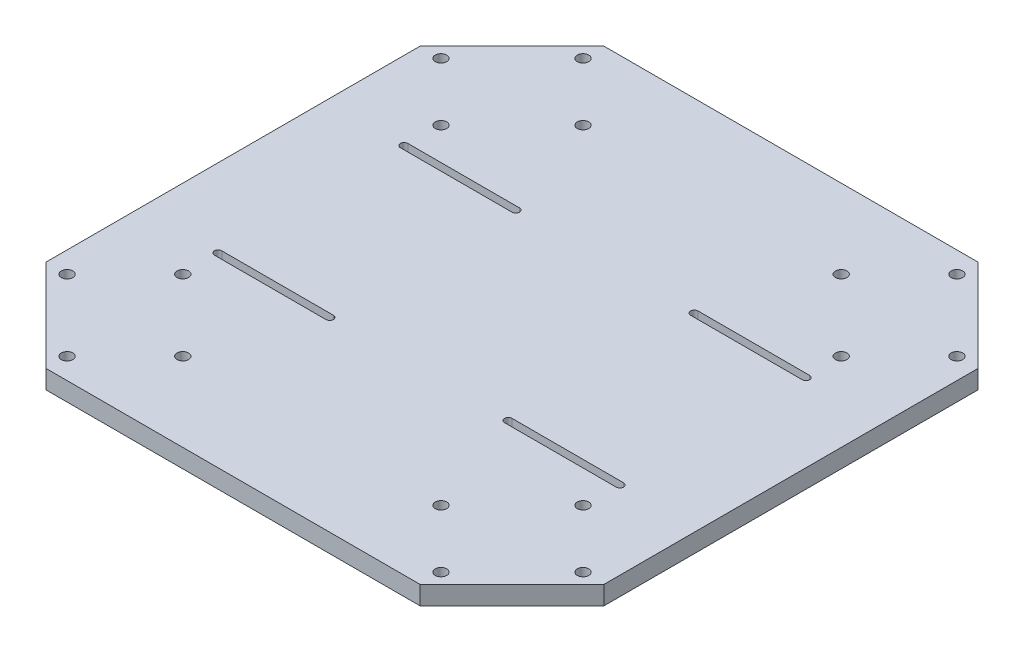
SolidWorks part; units mm, degrees
ref_plane "Front Plane" through (0, 0, 0) normal (0, 0, 1) x (1, 0, 0)
ref_plane "Top Plane" through (0, 0, 0) normal (0, 1, 0) x (1, 0, 0)
ref_plane "Right Plane" through (0, 0, 0) normal (1, 0, 0) x (0, 0, -1)
sketch "Sketch1" plane through (0, 0, 0) normal (0, 1, 0) x (1, 0, 0)
  line L1 (-75, 75) -> (75, 75)
  line L2 (-75, 75) -> (-75, -75)
  line L3 (-75, -75) -> (75, -75)
  line L4 (75, 75) -> (75, -75)
  line L5 (-75, 75) -> (75, -75) construction
  line L6 (-75, -75) -> (75, 75) construction
  point P0 (0, 0)
  dimension "D1" = 150
extrude "Boss-Extrude1" add sketch "Sketch1" along normal mid plane 5
sketch "Sketch2" plane through (0, 2.5, 0) normal (0, 1, 0) x (1, 0, 0)
  line L0 (50.2513, 75) -> (75, 75)
  line L1 (-15, 15) -> (15, 15)
  line L2 (-15, 15) -> (-15, -15)
  line L3 (-15, -15) -> (15, -15)
  line L4 (15, 15) -> (15, -15)
  line L5 (-15, 15) -> (15, -15) construction
  line L6 (-15, -15) -> (15, 15) construction
  line L7 (75, 75) -> (-75, 75) construction
  line L8 (75, -75) -> (75, 75) construction
  line L9 (75, 75) -> (75, 50.2513)
  line L10 (75, 50.2513) -> (50.2513, 75)
  line L11 (0, 0) -> (-24.6603, 0) construction
  line L12 (0, 0) -> (0, -37.7235) construction
  line L13 (-75, 75) -> (-75, 50.2513)
  line L14 (-50.2513, 75) -> (-75, 75)
  line L15 (-75, 50.2513) -> (-50.2513, 75)
  line L16 (-50.2513, -75) -> (-75, -75)
  line L17 (-75, -50.2513) -> (-50.2513, -75)
  line L18 (-75, -75) -> (-75, -50.2513)
  line L19 (75, -75) -> (75, -50.2513)
  line L20 (50.2513, -75) -> (75, -75)
  line L21 (75, -50.2513) -> (50.2513, -75)
  point P0 (0, 0)
  dimension "D1" = 30
  dimension "D2" = 35
extrude "Cut-Extrude1" cut sketch "Sketch2" against normal up to surface (5 mm away) contours L10 L0 L9 | L13 L15 L14 | L19 L21 L20 | L16 L18 L17 up to face at (0, -2.5, 0)
sketch "Sketch3" plane through (0, 2.5, 0) normal (0, 1, 0) x (1, 0, 0)
  line L0 (75, 50.2513) -> (50.2513, 75) construction
  line L1 (10, 10) -> (-10, 10)
  line L2 (10, 10) -> (10, -10)
  line L3 (10, -10) -> (-10, -10)
  line L4 (-10, 10) -> (-10, -10)
  line L5 (10, 10) -> (-10, -10) construction
  line L6 (10, -10) -> (-10, 10) construction
  line L7 (0, 0) -> (0, -7.7356) construction
  line L8 (0, 0) -> (-6.2026, 0) construction
  circle A2 centre (69.3431, 50.2513) radius 1.55
  circle A3 centre (53.7868, 34.6949) radius 1.55
  circle A5 centre (34.6949, 53.7868) radius 1.55
  circle A6 centre (50.2513, 69.3431) radius 1.55
  circle A7 centre (-69.3431, 50.2513) radius 1.55
  circle A8 centre (-53.7868, 34.6949) radius 1.55
  circle A11 centre (-34.6949, 53.7868) radius 1.55
  circle A12 centre (-50.2513, 69.3431) radius 1.55
  circle A13 centre (-53.7868, -34.6949) radius 1.55
  circle A14 centre (-69.3431, -50.2513) radius 1.55
  circle A17 centre (-34.6949, -53.7868) radius 1.55
  circle A18 centre (-50.2513, -69.3431) radius 1.55
  circle A19 centre (69.3431, -50.2513) radius 1.55
  circle A20 centre (53.7868, -34.6949) radius 1.55
  circle A23 centre (34.6949, -53.7868) radius 1.55
  circle A24 centre (50.2513, -69.3431) radius 1.55
  point P0 (0, 0)
  dimension "D2" = 13.5
  dimension "D4" = 3.1
  dimension "D6" = 22
  dimension "D8" = 4
  dimension "D3" = 13.5
  dimension "D1" = 20
extrude "Cut-Extrude2" cut sketch "Sketch3" against normal up to surface (5 mm away) contours A12 | A11 | A7 | A8 | A13 | A14 | A17 | A18 | A19 | A20 | A23 | A24 | A2 | A3 | A5 | A6 region at (69.3431, 2.5, -50.2513) region at (53.7868, 2.5, -34.6949) region at (34.6949, 2.5, -53.7868) region at (50.2513, 2.5, -69.3431) region at (-69.3431, 2.5, -50.2513) region at (-53.7868, 2.5, -34.6949) region at (-34.6949, 2.5, -53.7868) region at (-50.2513, 2.5, -69.3431) region at (-53.7868, 2.5, 34.6949) region at (-69.3431, 2.5, 50.2513) region at (-34.6949, 2.5, 53.7868) region at (-50.2513, 2.5, 69.3431) region at (69.3431, 2.5, 50.2513) region at (53.7868, 2.5, 34.6949) region at (34.6949, 2.5, 53.7868) region at (50.2513, 2.5, 69.3431) up to face at (0, -2.5, 0)
sketch "Sketch4" plane through (0, 2.5, 0) normal (0, 1, 0) x (1, 0, 0)
  line L0 (24, 25) -> (54, 25) construction
  line L3 (24, 26) -> (54, 26)
  line L4 (24, 24) -> (54, 24)
  line L5 (0, 0) -> (-18.2653, 0) construction
  line L6 (0, 0) -> (0, -14.1035) construction
  line L7 (75, -50.2513) -> (75, 50.2513) construction
  line L8 (24, -25) -> (54, -25) construction
  line L9 (24, -26) -> (54, -26)
  line L10 (24, -24) -> (54, -24)
  line L11 (-24, -25) -> (-54, -25) construction
  line L12 (-24, -26) -> (-54, -26)
  line L13 (-24, -24) -> (-54, -24)
  line L14 (-24, 25) -> (-54, 25) construction
  line L15 (-24, 26) -> (-54, 26)
  line L16 (-24, 24) -> (-54, 24)
  arc A2 (24, 26) -> (24, 24) centre (24, 25) ccw
  arc A3 (54, 24) -> (54, 26) centre (54, 25) ccw
  arc A4 (24, -26) -> (24, -24) centre (24, -25) cw
  arc A5 (54, -24) -> (54, -26) centre (54, -25) cw
  arc A6 (-24, -26) -> (-24, -24) centre (-24, -25) ccw
  arc A7 (-54, -24) -> (-54, -26) centre (-54, -25) ccw
  arc A8 (-24, 26) -> (-24, 24) centre (-24, 25) cw
  arc A9 (-54, 24) -> (-54, 26) centre (-54, 25) cw
  point P2 (39, 25)
  point P10 (55, 25)
  point P16 (39, -25)
  point P23 (-39, -25)
  point P30 (-39, 25)
  dimension "D1" = 1
  dimension "D2" = 30
  dimension "D3" = 24
  dimension "D4" = 20
extrude "Cut-Extrude3" cut sketch "Sketch4" against normal up to surface (5 mm away) up to face at (-34.6949, -2.5, -52.2368)
